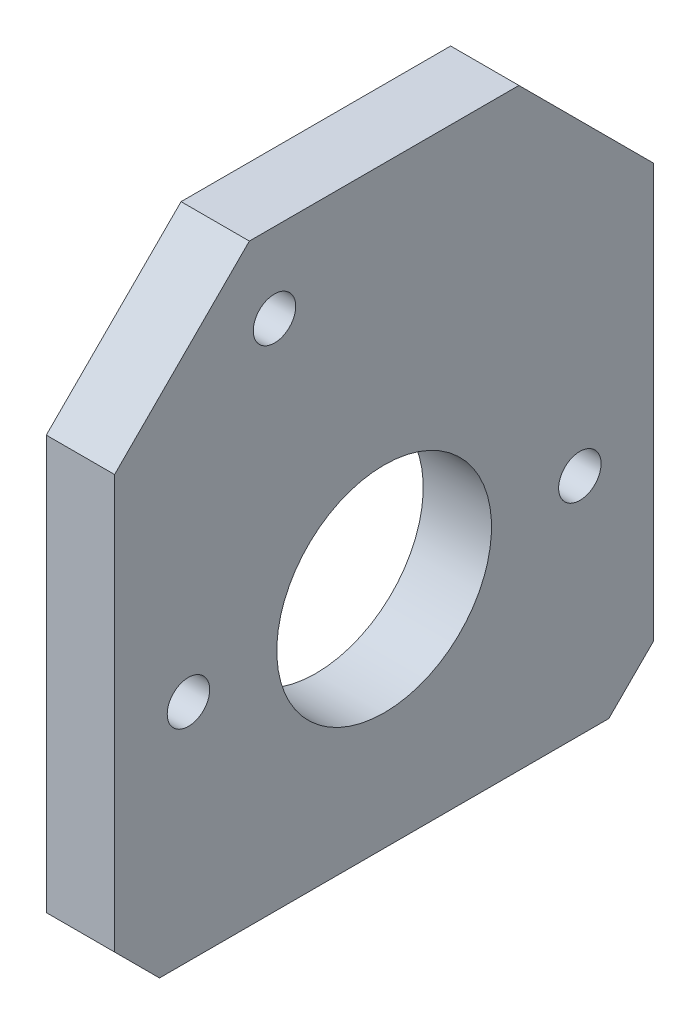
SolidWorks part; units mm, degrees
material "1060 Alloy"
ref_plane "Front" through (0, 0, 0) normal (0, 0, 1) x (1, 0, 0)
ref_plane "Top" through (0, 0, 0) normal (0, 1, 0) x (1, 0, 0)
ref_plane "Right" through (0, 0, 0) normal (1, 0, 0) x (0, 0, -1)
sketch "Sketch1" plane through (0, 0, 0) normal (1, 0, 0) x (0, 0, -1)
  line L0 (20.1279, -11.6427) -> (-11.6221, -11.6427) construction
  line L1 (-14.7971, 30.2823) -> (23.3029, 30.2823)
  line L2 (-14.7971, 30.2823) -> (-14.7971, -11.6427)
  line L3 (-14.7971, -11.6427) -> (23.3029, -11.6427)
  line L4 (23.3029, 30.2823) -> (23.3029, -11.6427)
  circle A1 centre (4.2529, 11.2323) radius 18.5 construction
  circle A5 centre (4.2529, 4.2323) radius 7.5875
  circle A6 centre (4.2529, 4.2323) radius 7.5875
  dimension "D1" = 19.05
  dimension "D2" = 19.05
  dimension "D3" = 19.05
  dimension "D5" = 1.5875
extrude "Boss-Extrude1" add sketch "Sketch1" along normal blind 4.826
hole_wizard "Ø3.0 (3) Diameter Hole1" positions "Sketch2" profile "Sketch3" hole size "Ø3.0" standard "ANSI Metric" end condition through all
sketch "Sketch2" plane through (0, 0, 0) normal (-1, 0, 0) x (0, 0, 1)
  point P0 (3.4971, 24.6557)
  point P3 (9.5764, 4.2323)
  point P6 (-18.0822, 4.2323)
sketch "Sketch3" plane through (0, 24.6557, 3.4971) normal (0, 1, 0) x (0, 0, 1)
  line L0 (0, 0) -> (0, 4.826)
  line L1 (0, 4.826) -> (1.5, 4.826)
  line L2 (1.5, 4.826) -> (1.5, 0)
  line L5 (1.5, 0) -> (0, 0)
  line L11 (0, -6.35) -> (0, 107.95) construction
  dimension "Thru Hole Dia." = 3
  dimension "Thru Hole Depth" = 4.826
chamfer "Chamfer1" distance 9.525 angle 45 2 edges at (2.413, 30.2823, -23.3029) (2.413, 30.2823, 14.7971)
chamfer "Chamfer2" distance 3.175 angle 45 2 edges at (2.413, -11.6427, 14.7971) (2.413, -11.6427, -23.3029)
